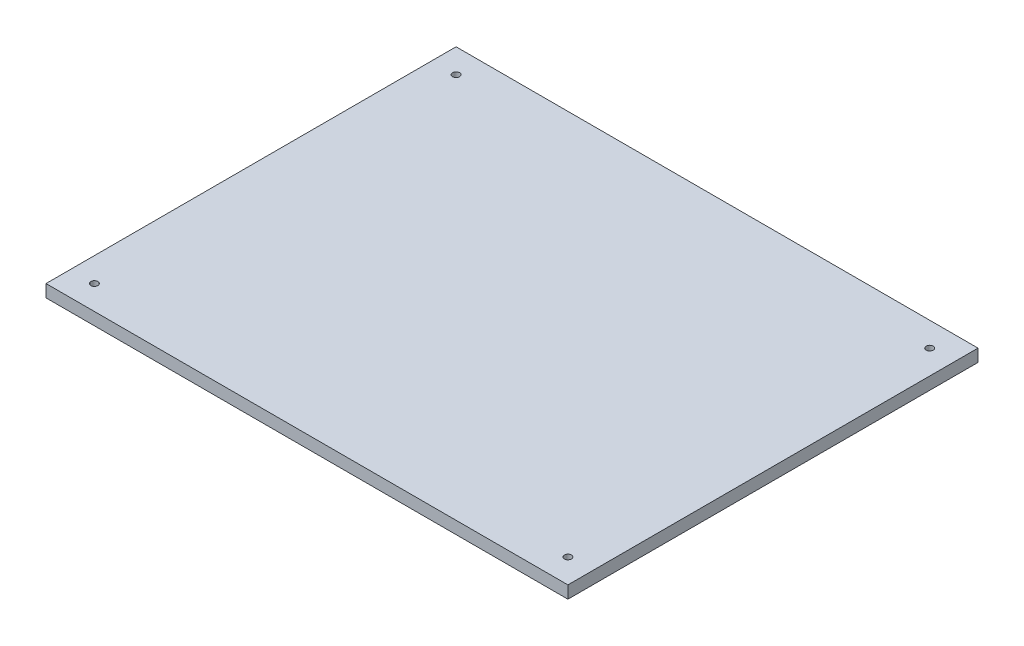
SolidWorks part; units mm, degrees
material "Acrylic (Medium-high impact)"
ref_plane "Front Plane" through (0, 0, 0) normal (0, 0, 1) x (1, 0, 0)
ref_plane "Top Plane" through (0, 0, 0) normal (0, 1, 0) x (1, 0, 0)
ref_plane "Right Plane" through (0, 0, 0) normal (1, 0, 0) x (0, 0, -1)
sketch "Sketch1" plane through (0, 0, 0) normal (0, 1, 0) x (1, 0, 0)
  line L1 (-133.35, 104.775) -> (133.35, 104.775)
  line L2 (-133.35, 104.775) -> (-133.35, -104.775)
  line L3 (-133.35, -104.775) -> (133.35, -104.775)
  line L4 (133.35, 104.775) -> (133.35, -104.775)
  line L5 (-133.35, 104.775) -> (133.35, -104.775) construction
  line L6 (-133.35, -104.775) -> (133.35, 104.775) construction
  point P0 (0, 0)
  dimension "D1" = 209.55
  dimension "D2" = 266.7
extrude "Boss-Extrude1" add sketch "Sketch1" along normal blind 6.35
hole_wizard "M3 Clearance Hole1" positions "Sketch2" profile "Sketch3" hole size "M3" standard "ANSI Metric" end condition through all
sketch "Sketch2" plane through (0, 6.35, 0) normal (0, 1, 0) x (1, 0, 0)
  line L0 (-133.35, -104.775) -> (133.35, -104.775) construction
  line L1 (133.35, -104.775) -> (133.35, 104.775) construction
  line L2 (133.35, 104.775) -> (-133.35, 104.775) construction
  line L3 (-133.35, 104.775) -> (-133.35, -104.775) construction
  point P0 (121.0056, -92.4306)
  point P2 (-121.0056, -92.4306)
  point P4 (-121.0056, 92.4306)
  point P6 (121.0056, 92.4306)
  dimension "D1" = 12.3444
  dimension "D2" = 12.3444
  dimension "D3" = 12.3444
  dimension "D4" = 12.3444
sketch "Sketch3" plane through (121.0056, 6.35, 92.4306) normal (1, 0, 0) x (0, 0, 1)
  line L0 (0, 0) -> (0, 6.35)
  line L1 (0, 6.35) -> (1.8, 6.35)
  line L2 (1.8, 6.35) -> (1.8, 0)
  line L5 (1.8, 0) -> (0, 0)
  line L11 (0, -6.35) -> (0, 107.95) construction
  dimension "Thru Hole Dia." = 3.6
  dimension "Thru Hole Depth" = 6.35
